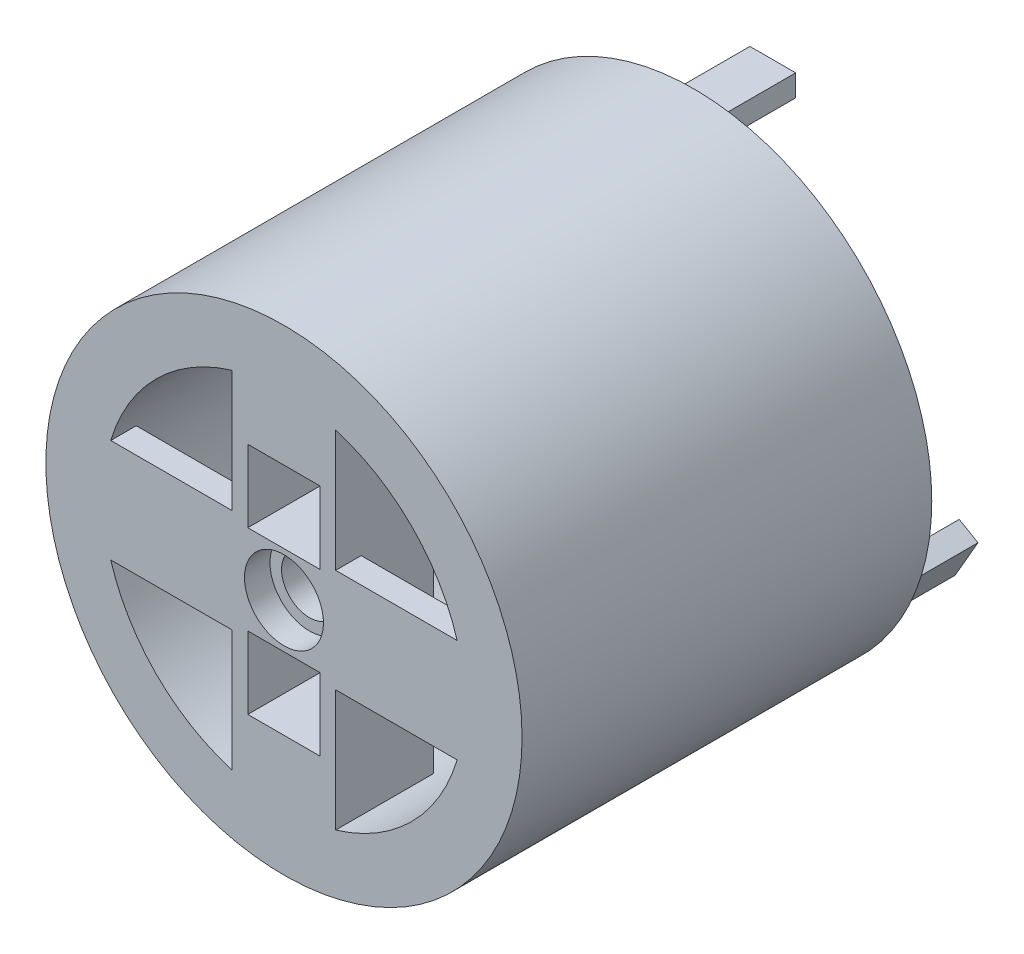
SolidWorks part; units mm, degrees
ref_plane "Front Plane" through (0, 0, 0) normal (0, 0, 1) x (1, 0, 0)
ref_plane "Top Plane" through (0, 0, 0) normal (0, 1, 0) x (1, 0, 0)
ref_plane "Right Plane" through (0, 0, 0) normal (1, 0, 0) x (0, 0, -1)
sketch "Sketch1" plane through (0, 0, 0) normal (0, 0, 1) x (1, 0, 0)
  line L0 (23.5, 0) -> (22.5, 0)
  line L1 (0, 25.15) -> (0, 22.5)
  line L3 (0, -22.5) -> (0, -29.64)
  line L4 (22.5, 0) -> (-22.5, 0)
  line L8 (28.3, 4.9) -> (23.5, 4.9)
  line L9 (28.3, 4.9) -> (28.3, -4.9)
  line L10 (28.3, -4.9) -> (23.5, -4.9)
  line L11 (23.5, 4.9) -> (23.5, -4.9)
  line L24 (-2.85, 27.85) -> (-2.85, 25.15)
  line L25 (-2.85, 27.85) -> (2.85, 27.85)
  line L26 (2.85, 27.85) -> (2.85, 25.15)
  line L27 (-2.85, 25.15) -> (2.85, 25.15)
  circle A0 centre (0, 0) radius 22.5
  circle A1 centre (0, 0) radius 29.64
  point P0 (0, 25.15)
  point P1 (23.5, 0)
  dimension "D3" = 5.7
  dimension "D1" = 1
  dimension "D2" = 2.65
  dimension "D4" = 2.7
extrude "Boss-Extrude1" add sketch "Sketch1" along normal blind 51 contours A1 L11 L8 L9 L10 L27 L24 L25 L26 A0 | L24 L27 L26 L25 | L8 L11 L10 L9 | L3 A1 L9 L10 L11 L0 A0 region at (-20.3658, 20.3658, 0) region at (0, 26.5, 0) region at (25.9, 0, 0)
extrude "Boss-Extrude2" add sketch "Sketch1<4>" against normal blind 9.85 contours L25 L26 L27 L24
sketch "Sketch1<4>" plane through (0, 0, 0) normal (0, 0, 1) x (1, 0, 0) same geometry as "Sketch1"
sketch "Sketch3" plane through (0, 0, 0) normal (0, 1, 0) x (1, 0, 0)
  line L0 (0, -26.5014) -> (0, 0)
pattern_circular "CirPattern2" count 3 over 360 about axis through (0, 0, 26.5014) along (0, 0, -1) of "Boss-Extrude2" reverse direction yes
sketch "Sketch4" plane through (0, 0, 51) normal (0, 0, 1) x (1, 0, 0)
  line L1 (6.4367, -24.2141) -> (-6.4367, -24.2141)
  line L2 (6.4367, -24.2141) -> (6.4367, 24.2141)
  line L3 (6.4367, 24.2141) -> (-6.4367, 24.2141)
  line L4 (-6.4367, -24.2141) -> (-6.4367, 24.2141)
  line L5 (6.4367, -24.2141) -> (-6.4367, 24.2141) construction
  line L6 (6.4367, 24.2141) -> (-6.4367, -24.2141) construction
  line L7 (-24.2141, 6.4367) -> (24.2141, 6.4367)
  line L8 (-24.2141, 6.4367) -> (-24.2141, -6.4367)
  line L9 (-24.2141, -6.4367) -> (24.2141, -6.4367)
  line L10 (24.2141, 6.4367) -> (24.2141, -6.4367)
  line L11 (-24.2141, 6.4367) -> (24.2141, -6.4367) construction
  line L12 (-24.2141, -6.4367) -> (24.2141, 6.4367) construction
  point P0 (0, 0)
  point P5 (0, 0)
  point P11 (6.4367, 24.2141)
  circle M5 centre (0, 0) radius 22.5
extrude "Boss-Extrude3" add sketch "Sketch4" against normal blind 3.175 contours L2 L9 L7 M5 | L9 L4 L2 M5 | L9 L10 L7 L8 | L2 L3 L4 L1 region at (0, -14.3154, 51) region at (14.3154, 0, 51)
sketch "Sketch7" plane through (0, 0, 51) normal (0, 0, 1) x (1, 0, 0)
  circle A0 centre (0, 0) radius 4.9125
extrude "Cut-Extrude2" cut sketch "Sketch7" against normal up to next and the other way through all
sketch "Sketch8" plane through (0, 0, 47.825) normal (0, 0, 1) x (1, 0, 0)
  line L0 (0, -3.475) -> (0, -24.0864)
  line L5 (6.4367, 24.0864) -> (-6.4367, 24.0864)
  line L6 (6.4367, 24.0864) -> (6.4367, -24.0864)
  line L11 (6.4367, -24.0864) -> (-6.4367, -24.0864)
  line L12 (-6.4367, 24.0864) -> (-6.4367, -24.0864)
  line L13 (6.4367, 24.0864) -> (-6.4367, -24.0864) construction
  line L14 (6.4367, -24.0864) -> (-6.4367, 24.0864) construction
  line L15 (6.4367, 6.4367) -> (6.4367, 21.5597) construction
  circle A1 centre (0, 0) radius 3.475
  point P0 (0, 0)
  dimension "D2" = 12.8734
extrude "Boss-Extrude4" add sketch "Sketch8" against normal blind 9 contours L5 L12 L11 L6 | A1
extrude "Cut-Extrude1" cut sketch "Sketch1<3>" along normal blind 23 contours L8 L11 L10 L9 region at (25.9, 0, 0)
sketch "Sketch1<3>" plane through (0, 0, 0) normal (0, 0, 1) x (1, 0, 0) same geometry as "Sketch1"
pattern_circular "CirPattern1" count 6 over 360 about axis through (0, 0, 26.5014) along (0, 0, -1) of "Cut-Extrude1" reverse direction yes
sketch "Sketch11" plane through (0, 0, 51) normal (0, 0, -1) x (-1, 0, 0)
  line L0 (0, 5.5625) -> (0, 4.9125)
  line L1 (-4.5, 14.5625) -> (4.5, 14.5625)
  line L2 (-4.5, 14.5625) -> (-4.5, 5.5625)
  line L3 (-4.5, 5.5625) -> (4.5, 5.5625)
  line L4 (4.5, 14.5625) -> (4.5, 5.5625)
  line L5 (-4.5, 14.5625) -> (4.5, 5.5625) construction
  line L6 (-4.5, 5.5625) -> (4.5, 14.5625) construction
  circle A0 centre (0, 0) radius 4.9125 construction
  point P0 (0, 10.0625)
  dimension "D1" = 9
extrude "Cut-Extrude21" cut sketch "Sketch11" along normal blind 29 contours L1 L4 L3 L2 region at (0, 10.0625, 51)
mirror "Mirror1" about plane through (0, 0, 0) normal (0, 1, 0) of "Cut-Extrude21"
